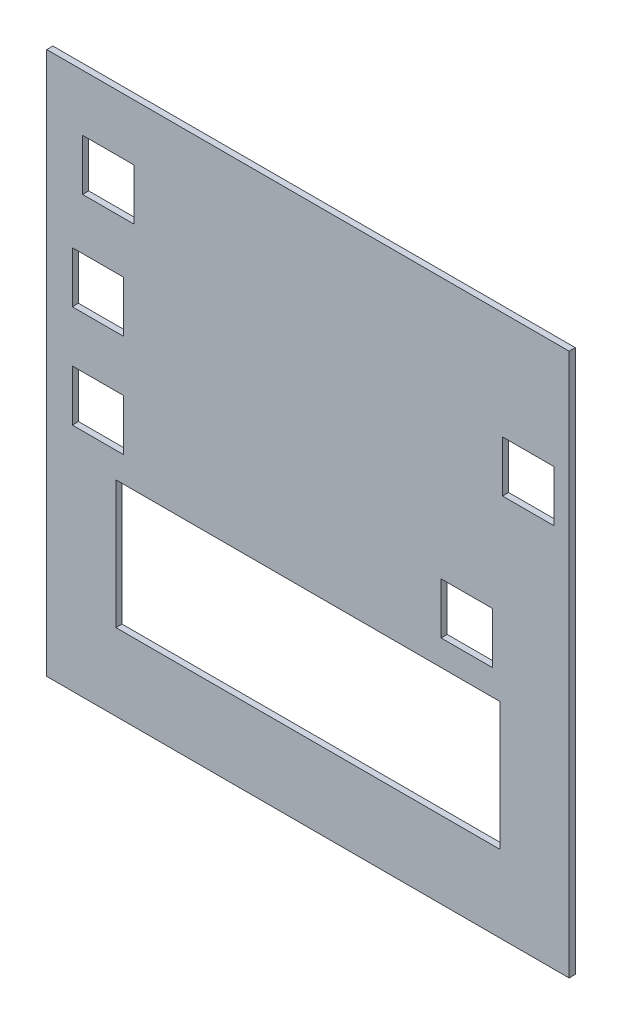
SolidWorks part; units mm, degrees
ref_plane "前视基准面" through (0, 0, 0) normal (0, 0, 1) x (1, 0, 0)
ref_plane "上视基准面" through (0, 0, 0) normal (0, 1, 0) x (1, 0, 0)
ref_plane "右视基准面" through (0, 0, 0) normal (1, 0, 0) x (0, 0, -1)
sketch "草图1" plane through (0, 0, 0) normal (0, 0, 1) x (1, 0, 0)
  line L1 (-51, 53) -> (51, 53)
  line L2 (-51, 53) -> (-51, -53)
  line L3 (-51, -53) -> (51, -53)
  line L4 (51, 53) -> (51, -53)
  line L5 (-51, 53) -> (51, -53) construction
  line L6 (-51, -53) -> (51, 53) construction
  point P0 (0, 0)
  dimension "D1" = 102
  dimension "D2" = 106
extrude "凸台-拉伸1" add sketch "草图1" along normal blind 1.2
sketch "草图2" plane through (0, 0, 1.2) normal (0, 0, 1) x (1, 0, 0)
  line L0 (-51, -53) -> (51, -53) construction
  line L1 (37.5, -13) -> (-37.5, -13)
  line L2 (37.5, -13) -> (37.5, -38)
  line L3 (37.5, -38) -> (-37.5, -38)
  line L4 (-37.5, -13) -> (-37.5, -38)
  line L5 (37.5, -13) -> (-37.5, -38) construction
  line L6 (37.5, -38) -> (-37.5, -13) construction
  line L7 (-51, 53) -> (-51, -53) construction
  point P0 (0, -25.5)
  dimension "D1" = 15
  dimension "D2" = 75
  dimension "D3" = 25
  dimension "D4" = 13.5
extrude "切除-拉伸2" cut sketch "草图2" against normal blind 10 and the other way blind 10
sketch "草图3" plane through (0, 0, 1.2) normal (0, 0, 1) x (1, 0, 0)
  line L0 (-51, 53) -> (-51, -53) construction
  line L1 (-36, -8) -> (-46, -8)
  line L2 (-36, -8) -> (-36, 2)
  line L3 (-36, 2) -> (-46, 2)
  line L4 (-46, -8) -> (-46, 2)
  line L5 (-36, -8) -> (-46, 2) construction
  line L6 (-36, 2) -> (-46, -8) construction
  line L7 (51, -53) -> (51, 53) construction
  line L9 (-51, -53) -> (51, -53) construction
  line L11 (36, -8) -> (26, -8)
  line L12 (36, -8) -> (36, 2)
  line L13 (36, 2) -> (26, 2)
  line L14 (26, -8) -> (26, 2)
  line L15 (36, -8) -> (26, 2) construction
  line L16 (36, 2) -> (26, -8) construction
  point P0 (-41, -3)
  point P7 (0, 0)
  point P11 (31, -3)
  dimension "D1" = 10
  dimension "D2" = 10
  dimension "D3" = 10
  dimension "D4" = 50
  dimension "D5" = 50
  dimension "D6" = 20
extrude "切除-拉伸3" cut sketch "草图3" against normal blind 10 and the other way blind 10
sketch "草图4" plane through (0, 0, 1.2) normal (0, 0, 1) x (1, 0, 0)
  line L0 (-51, -53) -> (51, -53) construction
  line L1 (-46, 22) -> (-36, 22)
  line L2 (-46, 22) -> (-46, 12)
  line L3 (-46, 12) -> (-36, 12)
  line L4 (-36, 22) -> (-36, 12)
  line L5 (-46, 22) -> (-36, 12) construction
  line L6 (-46, 12) -> (-36, 22) construction
  line L7 (-51, 53) -> (-51, -53) construction
  line L9 (-34, 32) -> (-44, 32)
  line L10 (-34, 32) -> (-34, 42)
  line L11 (-34, 42) -> (-44, 42)
  line L12 (-44, 32) -> (-44, 42)
  line L13 (-34, 32) -> (-44, 42) construction
  line L14 (-34, 42) -> (-44, 32) construction
  line L15 (-51, -53) -> (51, -53) construction
  line L16 (51, -53) -> (51, 53) construction
  line L17 (48, 22) -> (38, 22)
  line L18 (48, 22) -> (48, 32)
  line L19 (48, 32) -> (38, 32)
  line L20 (38, 22) -> (38, 32)
  line L21 (48, 22) -> (38, 32) construction
  line L22 (48, 32) -> (38, 22) construction
  point P0 (-41, 17)
  point P9 (43, 27)
  point P12 (-39, 37)
  dimension "D1" = 70
  dimension "D2" = 10
  dimension "D3" = 90
  dimension "D4" = 80
  dimension "D5" = 10
  dimension "D6" = 10
  dimension "D7" = 8
  dimension "D8" = 10
  dimension "D9" = 10
extrude "切除-拉伸4" cut sketch "草图4" against normal blind 10 and the other way blind 10
